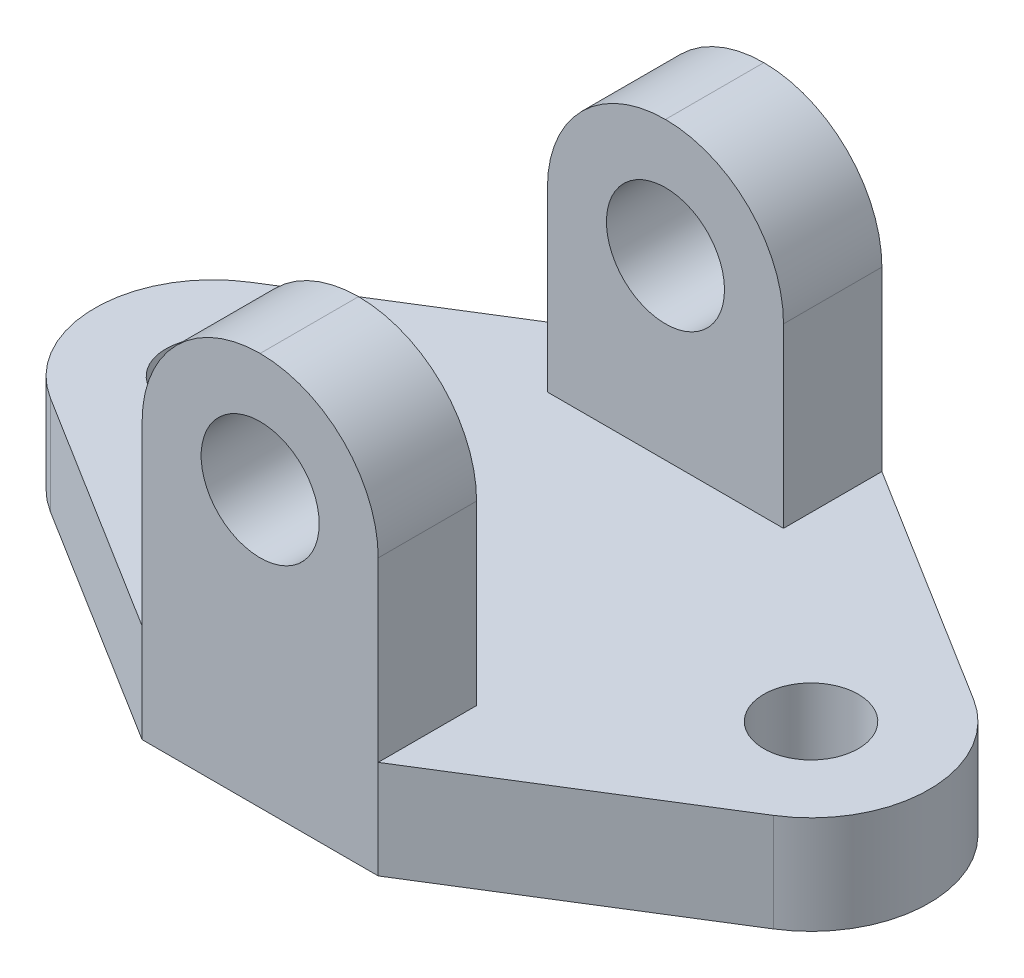
SolidWorks part; units mm, degrees
ref_plane "Front Plane" through (0, 0, 0) normal (0, 0, 1) x (1, 0, 0)
ref_plane "Top Plane" through (0, 0, 0) normal (0, 1, 0) x (1, 0, 0)
ref_plane "Right Plane" through (0, 0, 0) normal (1, 0, 0) x (0, 0, -1)
sketch "Sketch1" plane through (0, 0, 0) normal (0, 1, 0) x (1, 0, 0)
  line L0 (-482.3457, 0) -> (23634.9382, 0) construction
  line L1 (0, -482.3457) -> (0, 23634.9382) construction
  line L2 (-45.9311, 12.7317) -> (-15, 32)
  line L3 (45.9311, 12.7317) -> (15, 32)
  line L4 (-15, 32) -> (15, 32)
  line L5 (45.9311, -12.7317) -> (15, -32)
  line L6 (-15, -32) -> (15, -32)
  line L7 (-45.9311, -12.7317) -> (-15, -32)
  circle A0 centre (-38, 0) radius 6
  circle A1 centre (38, 0) radius 6
  arc A2 (-45.9311, 12.7317) -> (-45.9311, -12.7317) centre (-38, 0) ccw
  arc A3 (45.9311, 12.7317) -> (45.9311, -12.7317) centre (38, 0) cw
  point P15 (0, 32)
  dimension "D1" = 12
  dimension "D2" = 30
  dimension "D3" = 76
  dimension "D4" = 32
  dimension "D5" = 30
extrude "Boss-Extrude1" add sketch "Sketch1" along normal blind 12.5
sketch "Sketch2" plane through (0, 0, 32) normal (0, 0, 1) x (1, 0, 0)
  line L0 (0, -1000) -> (0, 49000) construction
  line L1 (-1000, 0) -> (49000, 0) construction
  line L3 (-15, 0) -> (15, 0)
  line L4 (-15, 0) -> (-15, 50)
  line L5 (-15, 50) -> (15, 50)
  line L6 (15, 0) -> (15, 50)
  line L7 (-15, 0) -> (15, 50) construction
  line L8 (-15, 50) -> (15, 0) construction
  circle A0 centre (0, 35) radius 7.5
  point P4 (0, 25)
  dimension "D4" = 15
  dimension "D1" = 50
  dimension "D2" = 30
  dimension "D3" = 35
extrude "Boss-Extrude2" add sketch "Sketch2" against normal blind 12.5
fillet "Fillet1" radius 15 2 edges at (15, 50, 25.75) (-15, 50, 25.75)
mirror "Mirror1" about plane through (0, 0, 0) normal (0, 0, 1) of "Fillet1", "Boss-Extrude2"
